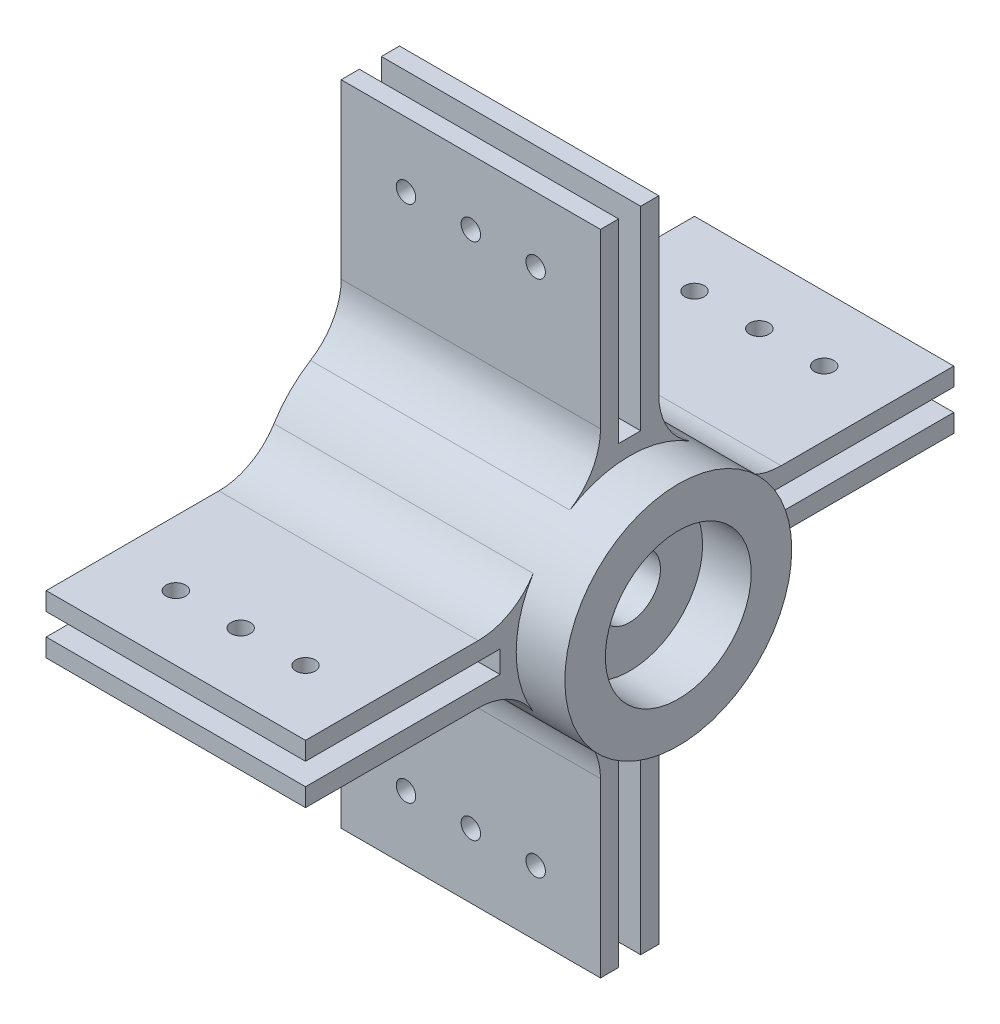
SolidWorks part; units mm, degrees
ref_plane "Front Plane" through (0, 0, 0) normal (0, 0, 1) x (1, 0, 0)
ref_plane "Top Plane" through (0, 0, 0) normal (0, 1, 0) x (1, 0, 0)
ref_plane "Right Plane" through (0, 0, 0) normal (1, 0, 0) x (0, 0, -1)
sketch "Sketch1" plane through (0, 0, 0) normal (1, 0, 0) x (0, 0, -1)
  circle A0 centre (0, 0) radius 17.5
  circle A1 centre (0, 0) radius 4.75
  dimension "D1" = 35
  dimension "D2" = 9.5
extrude "MainBody" add sketch "Sketch1" along normal blind 40
sketch "Sketch2" plane through (40, 0, 0) normal (1, 0, 0) x (0, 0, -1)
  circle A0 centre (0, 0) radius 17.5 construction
  circle A1 centre (0, 0) radius 17.5
  circle A2 centre (0, 0) radius 11.25
  dimension "D1" = 22.5
extrude "BearingHousing" add sketch "Sketch2" along normal blind 7.5
sketch "Sketch3" plane through (0, 0, 0) normal (-1, 0, 0) x (0, 0, 1)
  circle A0 centre (0, 13) radius 1.5
  circle A1 centre (11.2583, 6.5) radius 1.5
  circle A2 centre (11.2583, -6.5) radius 1.5
  circle A3 centre (0, -13) radius 1.5
  circle A4 centre (-11.2583, -6.5) radius 1.5
  circle A5 centre (-11.2583, 6.5) radius 1.5
  point P15 (0, 0)
  dimension "D1" = 3
  dimension "D2" = 13
extrude "MountingHoles" cut sketch "Sketch3" against normal blind 20
sketch "Sketch4" plane through (0, 0, 0) normal (-1, 0, 0) x (0, 0, 1)
  line L0 (0, 0) -> (0, 30) construction
  line L1 (-4.5, 16.9115) -> (-4.5, 50)
  line L2 (-4.5, 50) -> (-1.7, 50)
  line L3 (-1.7, 50) -> (-1.7, 20)
  line L4 (-1.7, 20) -> (1.7, 20)
  line L5 (1.7, 50) -> (1.7, 20)
  line L6 (4.5, 50) -> (1.7, 50)
  line L7 (4.5, 16.9115) -> (4.5, 50)
  circle A0 centre (0, 0) radius 17.5 construction
  arc A1 (4.5, 16.9115) -> (-4.5, 16.9115) centre (0, 0) ccw
  circle A3 centre (0, 0) radius 4.75 construction
  point P9 (0, 50)
  point P11 (0, 20)
  dimension "D1" = 30
  dimension "D2" = 4.5
  dimension "D3" = 50
  dimension "D4" = 1.7
  dimension "D5" = 30
  dimension "D6" = 2.8
extrude "Boss-Extrude3" add sketch "Sketch4" against normal blind 40
sketch "Sketch6" plane through (0, 0, -4.5) normal (0, 0, -1) x (-1, 0, 0)
  line L0 (-40, 50) -> (0, 50) construction
  line L1 (-40, 50) -> (-40, 16.9115) construction
  circle A0 centre (-30, 40) radius 1.5
  circle A1 centre (-20, 40) radius 1.5
  circle A2 centre (-10, 40) radius 1.5
  dimension "D1" = 10
  dimension "D2" = 3
  dimension "D3" = 10
  dimension "D5" = 10
  dimension "D4" = 3
extrude "Cut-Extrude2" cut sketch "Sketch6" against normal through all
fillet "Fillet1" radius 10 2 edges at (20, 16.9115, -4.5) (20, 16.9115, 4.5)
pattern_circular "CirPattern1" count 4 over 360 about axis through (40, 0, 0) along (-1, 0, 0) of "Boss-Extrude3", "Cut-Extrude2", "Fillet1" reverse direction yes
